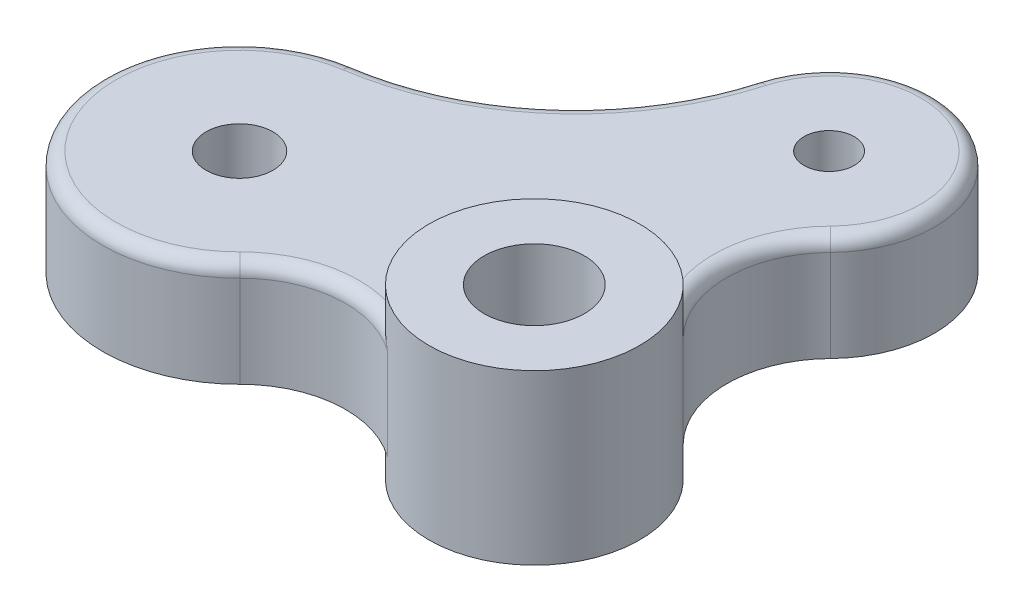
SolidWorks part; units mm, degrees
ref_plane "Front" through (0, 0, 0) normal (0, 0, 1) x (1, 0, 0)
ref_plane "Top" through (0, 0, 0) normal (0, 1, 0) x (1, 0, 0)
ref_plane "Right" through (0, 0, 0) normal (1, 0, 0) x (0, 0, -1)
sketch "Sketch2" plane through (0, 0, 0) normal (0, 1, 0) x (1, 0, 0)
  line L0 (-1000, 0) -> (49000, 0) construction
  line L1 (0, -1000) -> (0, 49000) construction
  circle A0 centre (0, 0) radius 25.0063
  circle A1 centre (0, 0) radius 11.9126
  arc A2 (17.8574, 52.4974) -> (-24.0523, 76.8438) centre (0, 70.0024) ccw
  arc A3 (17.8574, 52.4974) -> (17.8574, 17.505) centre (35.7058, 35.0012) ccw
  arc A4 (-74.851, 32.1356) -> (-46.9651, -22.9235) centre (-70.0024, 0) ccw
  arc A5 (-14.6278, -20.2816) -> (-46.9651, -22.9235) centre (-29.2482, -40.5528) ccw
  circle A6 centre (-70.0024, 0) radius 7.9375
  arc A8 (0, 70.0024) -> (-70.0024, 0) centre (0, 0) ccw construction
  arc A9 (-74.851, 32.1356) -> (-24.0523, 76.8438) centre (-84.1768, 93.9454) ccw
  circle A10 centre (0, 70.0024) radius 5.9563
  dimension "D1" = 50.0126
  dimension "D2" = 23.8252
  dimension "D3" = 50.0126
  dimension "D4" = 49.9872
  dimension "D6" = 15.875
  dimension "D7" = 64.9986
  dimension "D8" = 49.9872
  dimension "D10" = 11.9126
  dimension "D9" = 125.0188
  dimension "D5" = 70.0024
extrude "Boss-Extrude2" add sketch "Sketch2" along normal mid plane 40.005 contours A0 A1 region at (11.0692, 0, 21.6313)
extrude "Boss-Extrude3" add sketch "Sketch2<3>" along normal mid plane 24.9936 contours A9 A4 A5 A0 A3 A2 A10 A6 region at (-37.5333, 0, -26.9454)
sketch "Sketch2<3>" plane through (0, 0, 0) normal (0, 1, 0) x (1, 0, 0) same geometry as "Sketch2"
fillet "Fillet1" radius 3.175 5 edges at (10.7122, 12.4968, -35.0012) (12.5611, 12.4968, -91.6249) (-42.8786, 12.4968, -47.0212) (-31.2834, 12.4968, 15.6422) (-98.9952, 12.4968, 14.6841)
